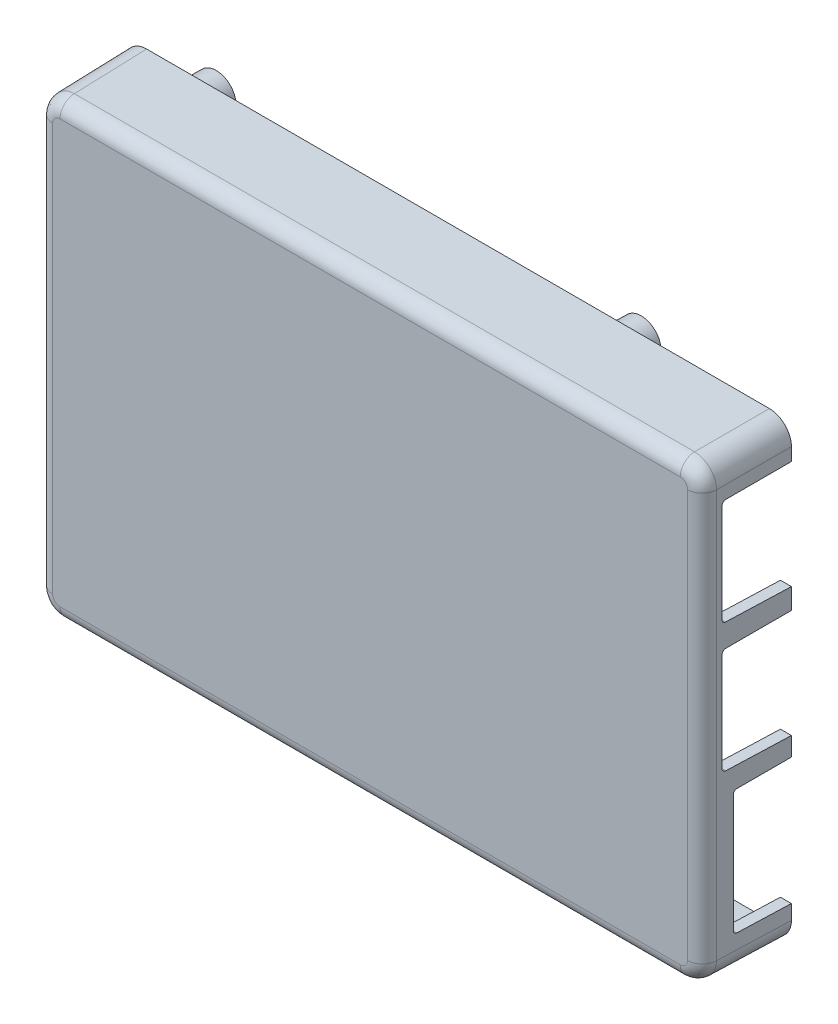
SolidWorks part; units mm, degrees
ref_plane "Front" through (0, 0, 0) normal (0, 0, 1) x (1, 0, 0)
ref_plane "Top" through (0, 0, 0) normal (0, 1, 0) x (1, 0, 0)
ref_plane "Right" through (0, 0, 0) normal (1, 0, 0) x (0, 0, -1)
sketch "Sketch1" plane through (0, 0, 0) normal (0, 0, 1) x (1, 0, 0)
  line L4 (-45.5, 31) -> (-45.5, -31)
  line L5 (-45.5, -31) -> (45.5, -31)
  line L6 (45.5, -31) -> (45.5, 31)
  line L7 (45.5, 31) -> (-45.5, 31)
  line L8 (-45.5, 31) -> (-45.5, -31)
  line L9 (-45.5, -31) -> (45.5, -31)
  line L10 (45.5, -31) -> (45.5, 31)
  line L11 (45.5, 31) -> (-45.5, 31)
  line L12 (-44, 29.5) -> (-44, -29.5)
  line L13 (-44, -29.5) -> (44, -29.5)
  line L14 (44, -29.5) -> (44, 29.5)
  line L15 (44, 29.5) -> (-44, 29.5)
  line L16 (-44, 29.5) -> (-44, -29.5)
  line L17 (-44, -29.5) -> (44, -29.5)
  line L18 (44, -29.5) -> (44, 29.5)
  line L19 (44, 29.5) -> (-44, 29.5)
  dimension "D1" = 0
  dimension "D2" = 0
extrude "Walls" add sketch "Sketch1" along normal blind 12
sketch "Sketch2" plane through (0, 0, 12) normal (0, 0, 1) x (1, 0, 0)
  line L4 (45.5, 31) -> (-45.5, 31)
  line L5 (-45.5, 31) -> (-45.5, -31)
  line L6 (-45.5, -31) -> (45.5, -31)
  line L7 (45.5, -31) -> (45.5, 31)
  line L8 (45.5, 31) -> (-45.5, 31)
  line L9 (-45.5, 31) -> (-45.5, -31)
  line L10 (-45.5, -31) -> (45.5, -31)
  line L11 (45.5, -31) -> (45.5, 31)
  dimension "D1" = 0
extrude "Base" add sketch "Sketch2" against normal blind 1.5
sketch "Sketch3" plane through (0, 0, 10.5) normal (0, 0, -1) x (-1, 0, 0)
  circle A0 centre (39, -24.5) radius 3
  circle A1 centre (-19, -24.5) radius 3
  circle A2 centre (-19, 24.5) radius 3
  circle A3 centre (39, 24.5) radius 3
  dimension "D1" = 6
extrude "Standoffs" add sketch "Sketch3" along normal blind 16.5 draft 1
hole_wizard "M2x0.4 Tapped Hole1" positions "Sketch4" profile "Sketch5" tap size "M2x0.4" standard "ANSI Metric"
sketch "Sketch4" plane through (0, 0, -6) normal (0, 0, -1) x (-1, 0, 0)
  point P0 (39, -24.5)
  point P3 (-19, -24.5)
  point P6 (-19, 24.5)
  point P9 (39, 24.5)
sketch "Sketch5" plane through (-39, -24.5, -6) normal (1, 0, 0) x (0, 1, 0)
  line L0 (0, 0) -> (0, 5.4807)
  line L1 (0, 5.4807) -> (0.8, 5)
  line L2 (0.8, 5) -> (0.8, 0)
  line L5 (0.8, 0) -> (0, 0)
  line L10 (0, 5.4807) -> (-0.8, 5) construction
  line L11 (0, -6.35) -> (0, 107.95) construction
  dimension "Tap Drill Dia." = 1.6
  dimension "Tap Drill Depth" = 5
  dimension "Drill Angle" = 118
cosmetic thread "Hole Thread1" parameters "D1"=4, "D2"=2
cosmetic thread "Hole Thread2" parameters "D1"=4, "D2"=2
cosmetic thread "Hole Thread3" parameters "D1"=4, "D2"=2
cosmetic thread "Hole Thread4" parameters "D1"=4, "D2"=2
sketch "Sketch6" plane through (0, 0, 0) normal (1, 0, 0) x (0, 0, -1)
  line L0 (5.9, -17.348) -> (-7.3, -17.348) construction
  line L1 (5.9, -19.848) -> (5.9, -14.848) construction
  line L2 (-7.3, -25.248) -> (-7.3, -9.448) construction
  line L3 (3.0235, -25.5) -> (5.6315, -25.5) construction
  line L4 (-7.8, -8.696) -> (6.4, -8.696)
  line L5 (-7.8, -8.696) -> (-7.8, -26)
  line L6 (-7.8, -26) -> (6.4, -26)
  line L7 (6.4, -8.696) -> (6.4, -26)
  line L8 (-7.8, -8.696) -> (6.4, -26) construction
  line L9 (-7.8, -26) -> (6.4, -8.696) construction
  line L10 (5.9, -25.248) -> (5.9, -24.4366) construction
  line L11 (-8.8, 1.25) -> (6.69, 1.25) construction
  line L12 (-8.8, 7.5) -> (-8.8, -5) construction
  line L13 (6.69, 7.74) -> (6.69, -5.24) construction
  line L14 (-8.25, 8.14) -> (6.69, 8.14) construction
  line L15 (-9.3, -6.14) -> (7.19, -6.14)
  line L16 (-9.3, -6.14) -> (-9.3, 8.64)
  line L17 (-9.3, 8.64) -> (7.19, 8.64)
  line L18 (7.19, -6.14) -> (7.19, 8.64)
  line L19 (-9.3, -6.14) -> (7.19, 8.64) construction
  line L20 (-9.3, 8.64) -> (7.19, -6.14) construction
  line L21 (-9.3, 11.46) -> (7.19, 11.46)
  line L22 (-9.3, 11.46) -> (-9.3, 26.24)
  line L23 (-9.3, 26.24) -> (7.19, 26.24)
  line L24 (7.19, 11.46) -> (7.19, 26.24)
  line L25 (-8.8, 18.85) -> (6.69, 18.85) construction
  line L26 (-9.3, 11.46) -> (7.19, 26.24) construction
  line L27 (-9.3, 26.24) -> (7.19, 11.46) construction
  line L28 (-8.8, 25.1) -> (-8.8, 12.6) construction
  point P6 (-0.7, -17.348)
  point P21 (-1.055, 1.25)
  point P33 (-1.055, 18.85)
  dimension "D1" = 0.5
  dimension "D2" = 0.5
  dimension "D3" = 0.5
  dimension "D4" = 0.5
  dimension "D5" = 2
extrude "USB and Ethernet Ports " cut sketch "Sketch6" along normal through all from offset 30
draft "Draft1" type of draft neutral plane draft angle 1 faces to draft 4 face at (45.5, 0.688, 4.8) face at (0, -31, 6) face at (-45.5, 0, 6) face at (0, 31, 6) neutral plane through (0, 0, 0) neutral plane normal (0, 0, -1) reverse direction yes parameters "D1"=1
draft "Draft2" type of draft neutral plane draft angle 1 faces to draft 4 face at (44, 0.688, 4.6125) face at (0, -29.5, 5.25) face at (-44, 0, 5.25) face at (0, 29.5, 5.25) neutral plane through (0, 0, 0) neutral plane normal (0, 0, -1) parameters "D1"=1
fillet "Fillet1" radius 3 4 edges at (-45.3953, 30.8953, 6) (45.3953, -30.8953, 6) (45.3953, 30.8953, 6) (-45.3953, -30.8953, 6)
fillet "Fillet2" radius 1.5 4 edges at (-43.9084, 29.4084, 5.25) (43.9084, -29.4084, 5.25) (43.9084, 29.4084, 5.25) (-43.9084, -29.4084, 5.25)
fillet "Fillet3" radius 2 8 edges at (44.412, 29.912, 12) (45.2905, 0, 12) (44.412, -29.912, 12) (0, -30.7905, 12) (-44.412, -29.912, 12) (-45.2905, 0, 12) (-44.412, 29.912, 12) (0, 30.7905, 12)
fillet "Fillet4" radius 0.5 12 edges at (-43.3775, -28.8775, 10.5) (0, -29.3167, 10.5) (43.3775, -28.8775, 10.5) (43.8167, 0, 10.5) (43.3775, 28.8775, 10.5) (0, 29.3167, 10.5) (-43.3775, 28.8775, 10.5) (-43.8167, 0, 10.5) (-36, -24.5, 10.5) (22, -24.5, 10.5) (22, 24.5, 10.5) (-36, 24.5, 10.5)
draft "Draft3" type of draft neutral plane draft angle 1 faces to draft 6 face at (44.6819, -26, 3.9) face at (44.6688, 11.46, 4.65) face at (44.6688, -6.14, 4.65) face at (44.6819, -8.696, 3.9) face at (44.6688, 8.64, 4.65) face at (44.6688, 26.24, 4.65) neutral plane through (0, 0, 0) neutral plane normal (0, 0, -1) parameters "D1"=1
fillet "Fillet5" radius 0.5 6 edges at (44.5877, 11.6223, 9.3) (44.5877, -5.9777, 9.3) (44.6139, -25.8639, 7.8) (44.6139, -8.8321, 7.8) (44.5877, 8.4777, 9.3) (44.5877, 26.0777, 9.3)
